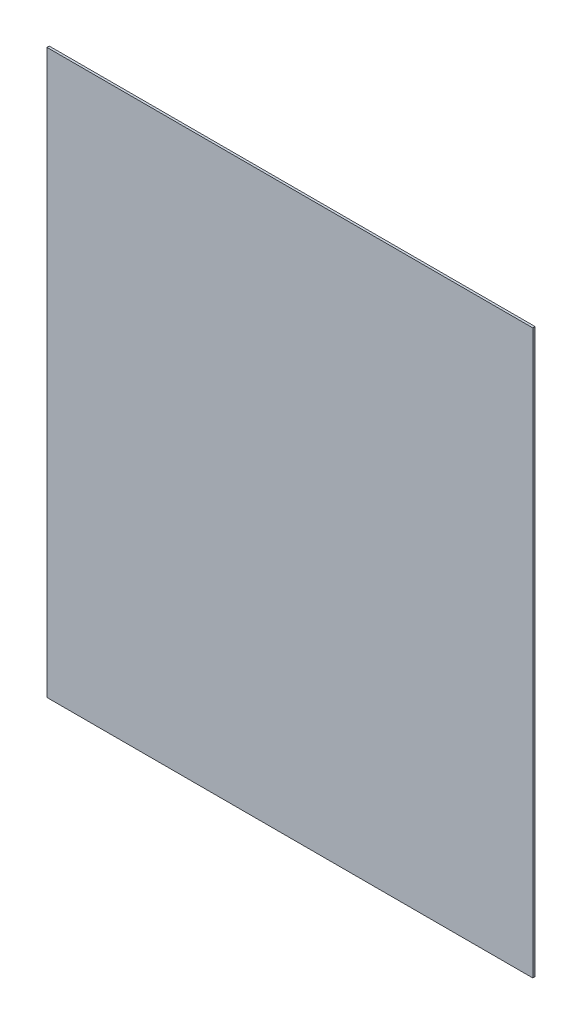
SolidWorks part; units mm, degrees
material "AISI 4130 Steel, normalized at 870C"
ref_plane "Front Plane" through (0, 0, 0) normal (0, 0, 1) x (1, 0, 0)
ref_plane "Top Plane" through (0, 0, 0) normal (0, 1, 0) x (1, 0, 0)
ref_plane "Right Plane" through (0, 0, 0) normal (1, 0, 0) x (0, 0, -1)
sketch "Sketch2" plane through (0, 0, 0) normal (0, 0, 1) x (1, 0, 0)
  line L1 (-155, 182.5) -> (160, 182.5)
  line L2 (-155, 182.5) -> (-155, -182.5)
  line L3 (-155, -182.5) -> (160, -182.5)
  line L4 (160, 182.5) -> (160, -182.5)
  dimension "D1" = 315
  dimension "D2" = 365
  dimension "D3" = 182.5
  dimension "D4" = 155
extrude "Boss-Extrude2" add sketch "Sketch2" along normal blind 1.5
